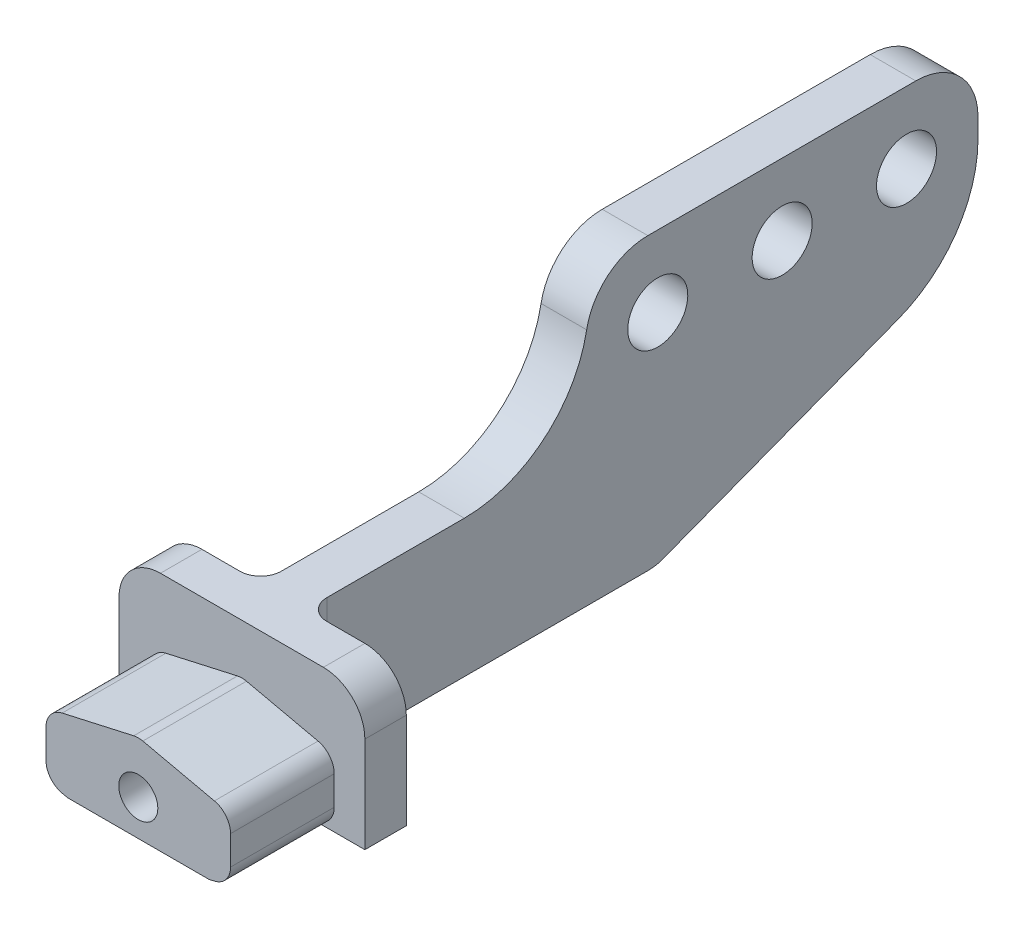
SolidWorks part; units mm, degrees
ref_plane "Front Plane" through (0, 0, 0) normal (0, 0, 1) x (1, 0, 0)
ref_plane "Top Plane" through (0, 0, 0) normal (0, 1, 0) x (1, 0, 0)
ref_plane "Right Plane" through (0, 0, 0) normal (1, 0, 0) x (0, 0, -1)
sketch "Sketch3" plane through (0, 0, 0) normal (0, 0, 1) x (1, 0, 0)
  line L1 (-2.965, 4.886) -> (2.965, 4.886)
  line L2 (-2.965, 4.886) -> (-2.965, 0)
  line L3 (-2.965, 0) -> (2.965, 0)
  line L4 (2.965, 4.886) -> (2.965, 0)
  dimension "D1" = 4.886
  dimension "D2" = 5.93
extrude "Mount Base Plate" add sketch "Sketch3" along normal blind 1
sketch "Horn Lever Profile" plane through (0, 0, 0) normal (0, 0, 1) x (1, 0, 0)
  line L0 (0, 1.576) -> (0, 0) construction
  line L1 (-0.55, 1.576) -> (0.55, 1.576)
  line L2 (-0.55, 1.576) -> (-0.55, 8.576)
  line L3 (-0.55, 8.576) -> (0.55, 8.576)
  line L4 (0.55, 1.576) -> (0.55, 8.576)
  line L5 (-2.965, 0) -> (2.965, 0) construction
  line L6 (-2.965, 0) -> (2.965, 0) construction
  dimension "D1" = 8.576
  dimension "D2" = 1.1
  dimension "D3" = 7
extrude "Lever Profile" add sketch "Horn Lever Profile" against normal blind 16.204
sketch "Lower CH Front Divot" plane through (0.55, 0, 0) normal (1, 0, 0) x (0, 0, -1)
  line L0 (0, 4.886) -> (6.814, 4.886)
  line L1 (6.814, 4.886) -> (6.814, 8.576)
  line L2 (16.204, 8.576) -> (0, 8.576) construction
  line L3 (6.814, 8.576) -> (0, 8.576)
  line L4 (0, 8.576) -> (0, 4.886)
  line L5 (16.204, 1.576) -> (16.204, 8.576) construction
  dimension "D1" = 9.39
extrude "Front Base Profile Cut" cut sketch "Lower CH Front Divot" against normal through all
sketch "Sketch6" plane through (0.55, 0, 0) normal (1, 0, 0) x (0, 0, -1)
  line L0 (8.434, 1.576) -> (16.204, 4.5477)
  line L1 (16.204, 1.576) -> (0, 1.576) construction
  line L2 (16.204, 1.576) -> (16.204, 8.576) construction
  line L3 (16.204, 4.5477) -> (16.204, 1.576)
  line L4 (16.204, 1.576) -> (8.434, 1.576)
  dimension "D1" = 7.77
  dimension "D2" = 20.93
extrude "Rear Profile Cut" cut sketch "Sketch6" against normal through all
sketch "3 Holes" plane through (0.55, 0, 0) normal (1, 0, 0) x (0, 0, -1)
  line L1 (16.204, 4.5477) -> (16.204, 8.576) construction
  line L2 (8.4801, 6.8521) -> (11.4801, 6.8521) construction
  line L3 (11.4801, 6.8521) -> (14.4801, 6.8521) construction
  line L8 (16.204, 8.576) -> (6.814, 8.576) construction
  circle A0 centre (14.4801, 6.8521) radius 0.7239
  circle A1 centre (11.4801, 6.8521) radius 0.7239
  circle A2 centre (8.4801, 6.8521) radius 0.7239
  dimension "D1" = 1.4478
  dimension "D2" = 1
  dimension "D3" = 1
  dimension "D4" = 3
extrude "3 Holes Ciut" cut sketch "3 Holes" against normal through all
sketch "Thru Surface Base Ext" plane through (0, 0, 1) normal (0, 0, 1) x (1, 0, 0)
  line L0 (0, 3.693) -> (2.226, 3.193)
  line L1 (2.226, 3.193) -> (2.226, 1.693)
  line L2 (2.226, 1.693) -> (0, 1.193)
  line L3 (0, 3.693) -> (0, 1.193) construction
  line L4 (-2.226, 2.443) -> (2.226, 2.443) construction
  line L6 (-2.226, 1.693) -> (0, 1.193)
  line L7 (-2.226, 3.193) -> (-2.226, 1.693)
  line L8 (0, 3.693) -> (-2.226, 3.193)
  line L9 (-2.965, 4.886) -> (2.965, 0) construction
  point P10 (0, 2.443)
  dimension "D1" = 2.5
  dimension "D3" = 1.5
  dimension "D4" = 4.452
extrude "Thru Base Mount Tab" add sketch "Thru Surface Base Ext" along normal blind 2.5
sketch "Sketch9" plane through (0, 0, 3.5) normal (0, 0, 1) x (1, 0, 0)
  line L0 (0, 3.693) -> (0, 1.193) construction
  circle A0 centre (0, 2.443) radius 0.4712
  dimension "D1" = 0.9423
extrude "Thru Base Mount Tab Hole" cut sketch "Sketch9" against normal blind 4
fillet "Base Plate Corner Fillet" radius 1 4 edges at (-2.965, 4.886, 0.5) (2.965, 4.886, 0.5) (2.965, 0, 0.5) (-2.965, 0, 0.5)
fillet "Front Lever Under Fillet" radius 3 1 edges at (0, 4.886, -6.814)
fillet "Front Lever Top Fillets" radius 1.5 5 edges at (0.55, 8.231, -6.814) (0, 7.886, -6.814) (0, 8.576, -16.204) (-0.55, 8.231, -6.814) (0, 8.576, -6.814)
fillet "Rear Top Fillet" radius 3 1 edges at (0, 4.5477, -16.204)
fillet "Side Base Lever Arm Fillets" radius 0.5 2 edges at (-0.55, 3.231, 0) (0.55, 3.231, 0)
fillet "Thru base Mount Tab Fillets" radius 0.5 6 edges at (0, 3.693, 2.25) (-2.226, 3.193, 2.25) (-2.226, 1.693, 2.25) (0, 1.193, 2.25) (2.226, 1.693, 2.25) (2.226, 3.193, 2.25)
fillet "Bot MiidLever Angle Fillet" radius 1 1 edges at (0, 1.576, -8.434)
fillet "Bot  Back Base to Lever Fillet" radius 0.5
ref_plane "Plane1" through (0, 1.576, 0) normal (0, -1, 0) x (1, 0, 0)
other "SurfaceCut1"
